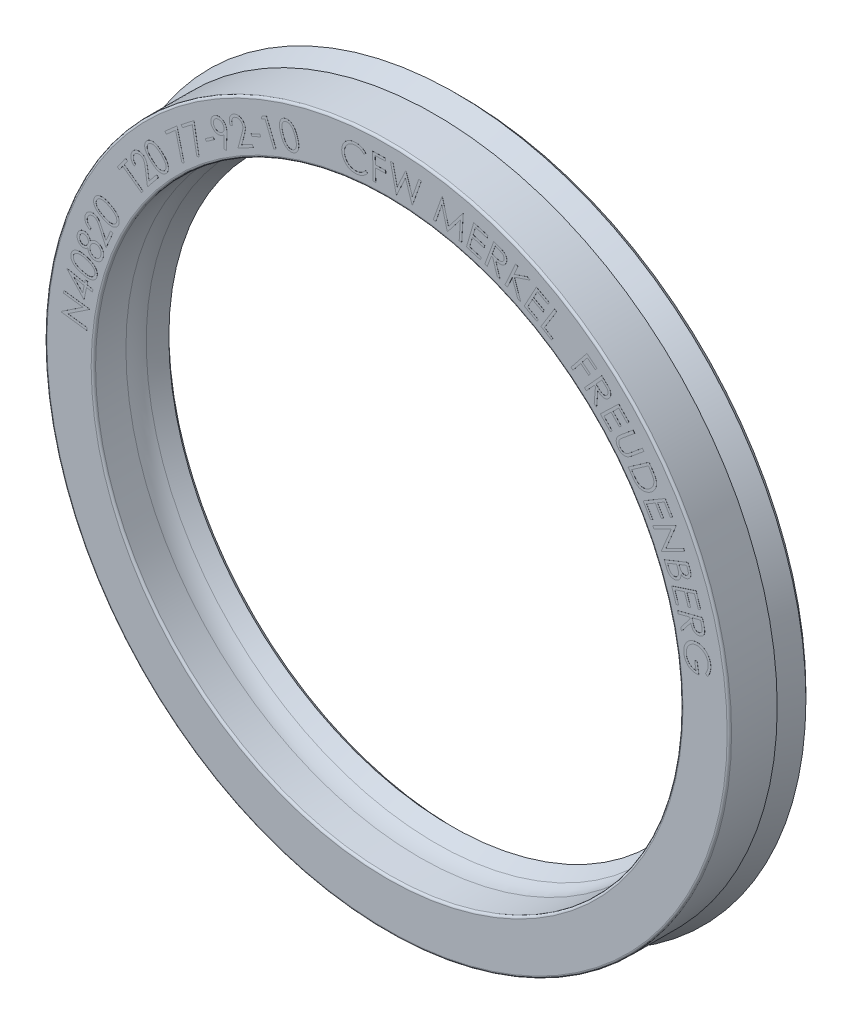
SolidWorks part; units mm, degrees
material "TPU-95A"
ref_plane "Front Plane" through (0, 0, 0) normal (0, 0, 1) x (1, 0, 0)
ref_plane "Top Plane" through (0, 0, 0) normal (0, 1, 0) x (1, 0, 0)
ref_plane "Right Plane" through (0, 0, 0) normal (1, 0, 0) x (0, 0, -1)
sketch "Sketch1" plane through (0, 0, 0) normal (1, 0, 0) x (0, 0, -1)
  line L0 (0, 40.2) -> (0, 46.2)
  line L1 (0.3, 46.5) -> (6.5, 46.5)
  line L2 (6.5, 46.5) -> (9.4, 47.5)
  line L3 (9.4, 47.5) -> (10.2, 46.7)
  line L4 (10.2, 46.7) -> (10.2, 45.25)
  line L5 (10.2, 45.25) -> (6.7379, 43.7157)
  line L6 (0.3, 39.9) -> (4.4197, 39.9)
  line L8 (0, 0) -> (11.0087, 0) construction
  line L9 (6.7155, 42.9951) -> (9.4, 41.6)
  line L10 (9.4, 41.6) -> (9.4, 39.05)
  line L11 (9.4, 39.05) -> (8.7, 38.35)
  line L12 (8.7, 38.35) -> (6.6557, 39.3721)
  arc A0 (4.4197, 39.9) -> (6.6557, 39.3721) centre (4.4197, 34.9) cw
  arc A2 (0, 46.2) -> (0.3, 46.5) centre (0.3, 46.2) cw
  arc A3 (0.3, 39.9) -> (0, 40.2) centre (0.3, 40.2) cw
  arc A4 (6.7155, 42.9951) -> (6.7379, 43.7157) centre (6.9, 43.35) cw
  point P12 (5.6, 39.9)
  dimension "D8" = 86.7
  dimension "D9" = 3.3
  dimension "D19" = 0.3
  dimension "D18" = 0.4
  dimension "D11" = 5
  dimension "D1" = 95
  dimension "D2" = 93
  dimension "D3" = 79.8
  dimension "D4" = 76.7
  dimension "D5" = 83.2
  dimension "D6" = 90.5
  dimension "D7" = 10.2
  dimension "D10" = 3.7
  dimension "D12" = 0.8
  dimension "D13" = 78.1
  dimension "D14" = 45
  dimension "D15" = 45
  dimension "D17" = 0.8
  dimension "D20" = 4.6
revolve "Revolve1" add sketch "Sketch1" angle 360 about L8
sketch "Sketch2" plane through (0, 0, 0) normal (0, 0, 1) x (1, 0, 0)
  arc A0 (-33.0527, -24.2594) -> (33.8124, -23.1888) centre (0, 0) cw construction
  text T0 "N40820   T20 77-92-10    CFW MERKEL  FREUDENBERG"
  dimension "D1" = 41
extrude "Boss-Extrude1" add sketch "Sketch2" along normal blind 0.01
